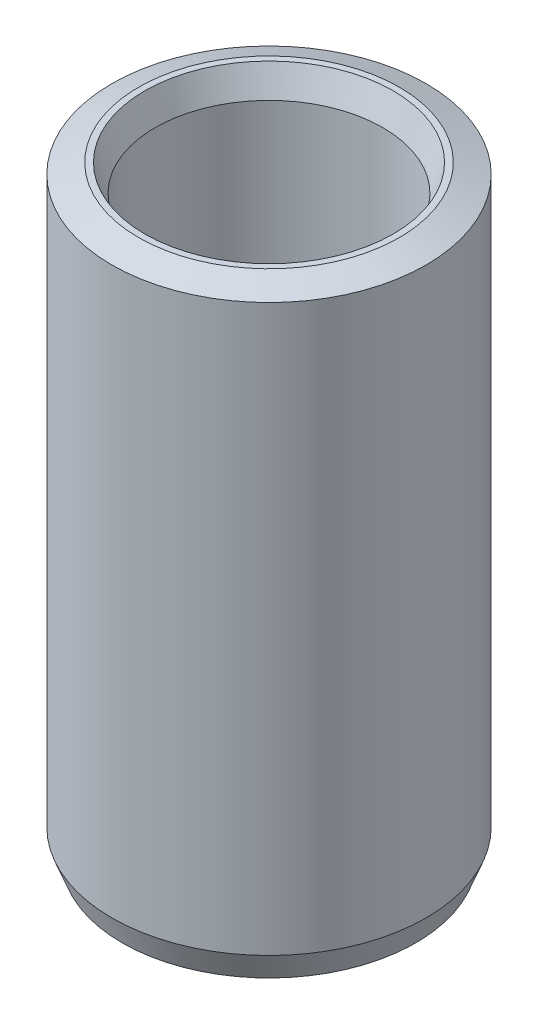
SolidWorks part; units mm, degrees
ref_plane "Front Plane" through (0, 0, 0) normal (0, 0, 1) x (1, 0, 0)
ref_plane "Top Plane" through (0, 0, 0) normal (0, 1, 0) x (1, 0, 0)
ref_plane "Right Plane" through (0, 0, 0) normal (1, 0, 0) x (0, 0, -1)
sketch "Sketch1" plane through (0, 0, 0) normal (0, 1, 0) x (1, 0, 0)
  circle A0 centre (0, 0) radius 50
  dimension "SLEEVE_OD" = 100
extrude "Boss-Extrude1" add sketch "Sketch1" along normal blind 191.7584
sketch "Sketch2" plane through (0, 0, 0) normal (0, 1, 0) x (1, 0, 0)
  circle A0 centre (0, 0) radius 36.2282
  dimension "BORE_D" = 72.4565
extrude "Cut-Extrude1" cut sketch "Sketch2" along normal through all
chamfer "Chamfer1" distance 3.2785 angle 68.958 4 edges at (0, 191.7584, 36.2282) (0, 0, 36.2282) (0, 0, 50) (0, 191.7584, 50) first distance on face at (0, 191.7584, 36.2282) first distance on face at (0, 0, 36.2282) first distance on face at (0, 191.7584, 50)
